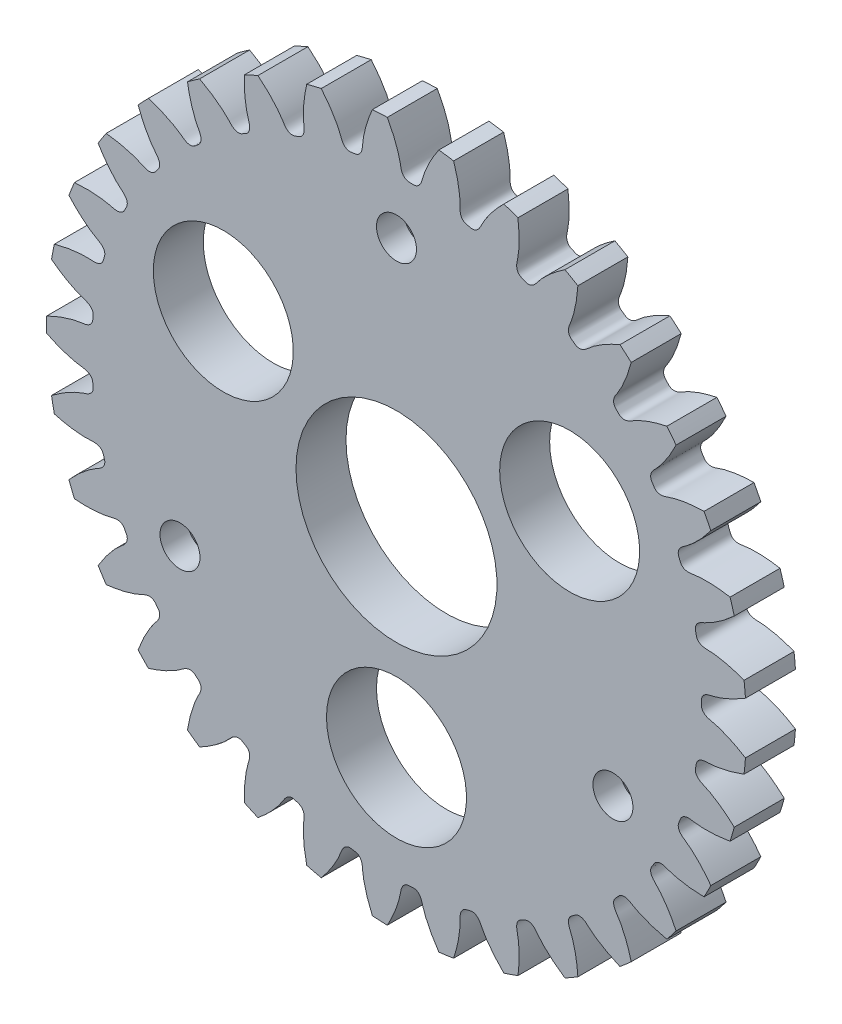
SolidWorks part; units mm, degrees
material "POM 乙缩醛共聚物"
ref_plane "前视基准面" through (0, 0, 0) normal (0, 0, 1) x (1, 0, 0)
ref_plane "上视基准面" through (0, 0, 0) normal (0, 1, 0) x (1, 0, 0)
ref_plane "右视基准面" through (0, 0, 0) normal (1, 0, 0) x (0, 0, -1)
ref_axis "基准轴1" through (0, 0, 55) along (0, 0, -1)
sketch "旋转草图小直齿轮" plane through (0, 0, 0) normal (1, 0, 0) x (0, 0, -1)
  line L0 (0, 0) -> (1, 0) construction
  line L1 (-2.5, 0) -> (-2.5, 35)
  line L2 (-2.5, 35) -> (2.5, 35)
  line L3 (2.5, 35) -> (2.5, 0)
  line L4 (2.5, 0) -> (-2.5, 0)
  dimension "D1" = 5
  dimension "D2" = 35
revolve "小直齿轮" add sketch "旋转草图小直齿轮" angle 360 about L0
sketch "齿草图小直齿轮" plane through (0, 0, 0) normal (0, 0, 1) x (1, 0, 0)
  arc A0 (35.0003, 2.644) -> (35.0003, -2.644) centre (0, 0) cw
  spline S0 degree 3 poles (35.0003, -2.644) (34.9194, -2.5929) (34.8115, -2.5261) (34.6765, -2.4448) (34.5971, -2.3976) (34.5183, -2.3514) (34.4402, -2.3062) (34.3628, -2.262) (34.2861, -2.2188) (34.21, -2.1766) (34.1347, -2.1353) (34.06, -2.0951) (33.9861, -2.0557) (33.9129, -2.0173) (33.8405, -1.9799) (33.7688, -1.9433) (33.6979, -1.9077) (33.6277, -1.873) (33.5583, -1.8392) (33.4897, -1.8062) (33.4218, -1.7741) (33.3548, -1.7429) (33.2886, -1.7126) (33.2231, -1.683) (33.1585, -1.6543) (33.0947, -1.6265) (33.0318, -1.5994) (32.9697, -1.5731) (32.9084, -1.5476) (32.848, -1.5229) (32.7885, -1.4989) (32.7298, -1.4757) (32.672, -1.4532) (32.6151, -1.4315) (32.5591, -1.4105) (32.5039, -1.3902) (32.4497, -1.3706) (32.3964, -1.3516) (32.344, -1.3334) (32.2925, -1.3158) (32.2419, -1.2988) (32.1923, -1.2825) (32.1436, -1.2669) (32.0958, -1.2518) (32.049, -1.2373) (32.0032, -1.2235) (31.9583, -1.2102) (31.9144, -1.1974) (31.8714, -1.1853) (31.8295, -1.1736) (31.7885, -1.1626) (31.7484, -1.152) (31.7094, -1.1419) (31.6714, -1.1323) (31.6344, -1.1233) (31.5983, -1.1146) (31.5633, -1.1065) (31.5293, -1.0988) (31.4963, -1.0915) (31.4002, -1.071) (31.2954, -1.0493) (31.1851, -1.0154) (31.1295, -0.9964) (31.0749, -0.9753) (31.0212, -0.952) (30.9679, -0.9261) (30.915, -0.897) (30.8622, -0.864) (30.8093, -0.8262) (30.7564, -0.7824) (30.7037, -0.7311) (30.652, -0.6706) (30.603, -0.5994) (30.5594, -0.5163) (30.5247, -0.4212) (30.5041, -0.3216) (30.4957, -0.18) (30.503, 0) (30.4957, 0.18) (30.5041, 0.3216) (30.5247, 0.4212) (30.5594, 0.5163) (30.603, 0.5994) (30.652, 0.6706) (30.7037, 0.7311) (30.7564, 0.7824) (30.8093, 0.8262) (30.8622, 0.864) (30.915, 0.897) (30.9679, 0.9261) (31.0212, 0.952) (31.0749, 0.9753) (31.1295, 0.9964) (31.1851, 1.0154) (31.2954, 1.0493) (31.4002, 1.071) (31.4963, 1.0915) (31.5293, 1.0988) (31.5633, 1.1065) (31.5983, 1.1146) (31.6344, 1.1233) (31.6714, 1.1323) (31.7094, 1.1419) (31.7484, 1.152) (31.7885, 1.1626) (31.8295, 1.1736) (31.8714, 1.1853) (31.9144, 1.1974) (31.9583, 1.2102) (32.0032, 1.2235) (32.049, 1.2373) (32.0958, 1.2518) (32.1436, 1.2669) (32.1923, 1.2825) (32.2419, 1.2988) (32.2925, 1.3158) (32.344, 1.3334) (32.3964, 1.3516) (32.4497, 1.3706) (32.5039, 1.3902) (32.5591, 1.4105) (32.6151, 1.4315) (32.672, 1.4532) (32.7298, 1.4757) (32.7885, 1.4989) (32.848, 1.5229) (32.9084, 1.5476) (32.9697, 1.5731) (33.0318, 1.5994) (33.0947, 1.6265) (33.1585, 1.6543) (33.2231, 1.683) (33.2886, 1.7126) (33.3548, 1.7429) (33.4218, 1.7741) (33.4897, 1.8062) (33.5583, 1.8392) (33.6277, 1.873) (33.6979, 1.9077) (33.7688, 1.9433) (33.8405, 1.9799) (33.9129, 2.0173) (33.9861, 2.0557) (34.06, 2.0951) (34.1347, 2.1353) (34.21, 2.1766) (34.2861, 2.2188) (34.3628, 2.262) (34.4402, 2.3062) (34.5183, 2.3514) (34.5971, 2.3976) (34.6765, 2.4448) (34.8115, 2.5261) (34.9194, 2.5929) (35.0003, 2.644) knots 0 0 0 0 0.026002 0.034472 0.042844 0.051118 0.059293 0.067371 0.075349 0.08323 0.091012 0.098696 0.106281 0.113768 0.121157 0.128447 0.135639 0.142732 0.149728 0.156625 0.163423 0.170123 0.176725 0.183229 0.189634 0.195941 0.202149 0.208259 0.214271 0.220184 0.226 0.231716 0.237335 0.242855 0.248276 0.2536 0.258825 0.263951 0.26898 0.273909 0.278741 0.283474 0.288109 0.292646 0.297084 0.301424 0.305665 0.309808 0.313853 0.317799 0.321647 0.325397 0.329049 0.332602 0.336056 0.339413 0.342671 0.34583 0.348892 0.351854 0.372547 0.377916 0.383228 0.388513 0.393806 0.39915 0.404598 0.410211 0.416067 0.422255 0.428875 0.436033 0.443827 0.452318 0.461494 0.471242 0.47984 0.5 0.52016 0.528758 0.538506 0.547682 0.556173 0.563967 0.571125 0.577745 0.583933 0.589789 0.595402 0.60085 0.606194 0.611487 0.616772 0.622084 0.627453 0.648146 0.651108 0.65417 0.657329 0.660587 0.663944 0.667398 0.670951 0.674603 0.678353 0.682201 0.686147 0.690192 0.694335 0.698576 0.702916 0.707354 0.711891 0.716526 0.721259 0.726091 0.73102 0.736049 0.741175 0.7464 0.751724 0.757145 0.762665 0.768284 0.774 0.779816 0.785729 0.791741 0.797851 0.804059 0.810366 0.816771 0.823275 0.829877 0.836577 0.843375 0.850272 0.857268 0.864361 0.871553 0.878843 0.886232 0.893719 0.901304 0.908988 0.91677 0.924651 0.932629 0.940707 0.948882 0.957156 0.965528 0.973998 1 1 1 1
extrude "齿拉伸切除小直齿轮" cut sketch "齿草图小直齿轮" against normal blind 10 and the other way blind 10
pattern_circular "齿形小直齿轮" count 33 every 10.909 about axis through (0, 0, 55) along (0, 0, -1) of "齿拉伸切除小直齿轮"
sketch "辅助草图小直齿轮" plane through (0, 0, 0) normal (0, 0, 1) x (1, 0, 0)
  circle A0 centre (0, 0) radius 33 construction
  circle A1 centre (0, 0) radius 31.0099 construction
  circle A2 centre (0, 0) radius 31.4316 construction
  circle A3 centre (0, 0) radius 35 construction
  circle A4 centre (0, 0) radius 30.5 construction
  dimension "PitchDiameter" = 66
  dimension "BaseDiameter" = 62.0197
  dimension "FormDiameter" = 62.8631
  dimension "MajorDiameter" = 70
  dimension "MinorDiameter" = 61
sketch "草图1" plane through (0, 0, -2.5) normal (0, 0, -1) x (-1, 0, 0)
  line L0 (0, 0) -> (0, 16.1896) construction
  line L1 (0, 0) -> (17.3205, 10) construction
  circle A0 centre (0, 0) radius 10.05
  circle A1 centre (0, 0) radius 25 construction
  circle A2 centre (0, 25) radius 2
  circle A3 centre (21.6506, -12.5) radius 2
  circle A4 centre (-21.6506, -12.5) radius 2
  circle A5 centre (0, 0) radius 20 construction
  circle A6 centre (17.3205, 10) radius 7
  circle A7 centre (0, -20) radius 7
  circle A8 centre (-17.3205, 10) radius 7
  point P13 (0, 0)
  point P22 (0, 0)
  dimension "D1" = 20.1
  dimension "D2" = 50
  dimension "D3" = 4
  dimension "D5" = 40
  dimension "D6" = 14
  dimension "D7" = 60
  dimension "D4" = 3
  dimension "D8" = 3
extrude "切除-拉伸1" cut sketch "草图1" against normal blind 10
hole_wizard "打孔尺寸(%根据十字)槽沉头木螺钉的类型1" positions "3D草图1" profile "草图2" countersink size "M4" standard "GB" end condition through all
sketch3d "3D草图1"
  line L0 (0, 25, 2.5) -> (0, 25, -2.5) construction
  line L1 (-21.6506, -12.5, 2.5) -> (-21.6506, -12.5, -2.5) construction
  line L2 (21.6506, -12.5, 2.5) -> (21.6506, -12.5, -2.5) construction
  point P0 (0, 25, -2.5)
  point P4 (-21.6506, -12.5, -2.5)
  point P8 (21.6506, -12.5, -2.5)
sketch "草图2" plane through (0, 25, -2.5) normal (1, 0, 0) x (0, 1, 0)
  line L0 (0, 0) -> (0, 5)
  line L1 (0, 5) -> (2, 5)
  line L2 (2, 5) -> (2, 2.3)
  line L3 (2, 2.3) -> (4.3, 0)
  line L5 (4.3, 0) -> (0, 0)
  line L6 (-2, 2.3) -> (-4.3, 0) construction
  line L11 (0, -6.35) -> (0, 107.95) construction
  dimension "通孔孔直径" = 4
  dimension "通孔孔深度" = 5
  dimension "近端锥形沉头孔直径" = 8.6
  dimension "近端锥形沉头孔角度" = 90
